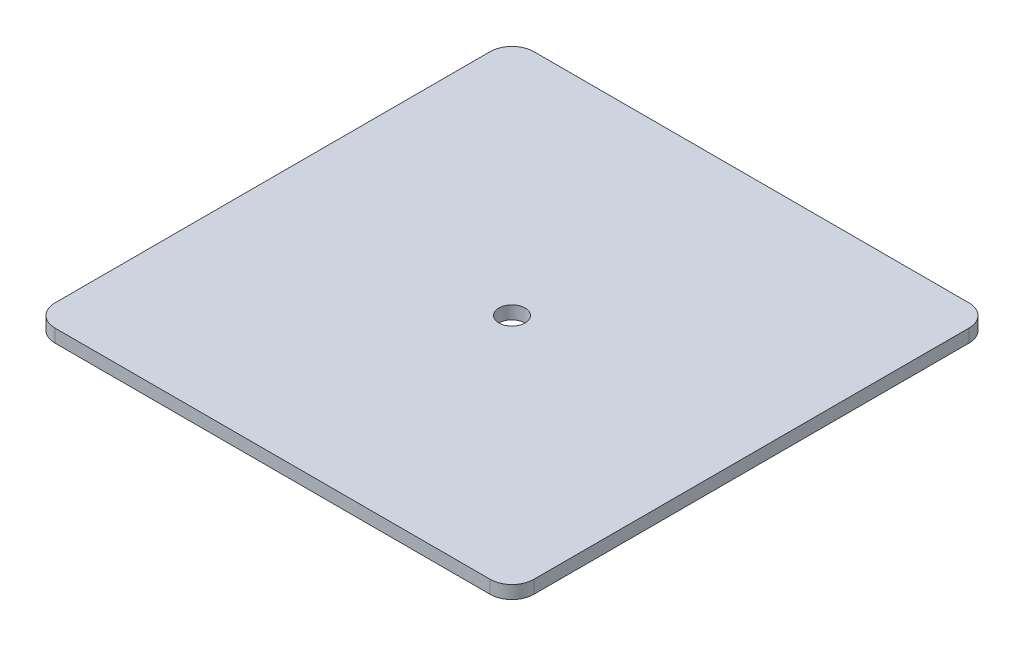
SolidWorks part; units mm, degrees
material "Acrylic (Medium-high impact)"
ref_plane "Front" through (0, 0, 0) normal (0, 0, 1) x (1, 0, 0)
ref_plane "Top" through (0, 0, 0) normal (0, 1, 0) x (1, 0, 0)
ref_plane "Right" through (0, 0, 0) normal (1, 0, 0) x (0, 0, -1)
sketch "Sketch1" plane through (0, 0, 0) normal (0, 1, 0) x (1, 0, 0)
  line L1 (110, -110) -> (-110, -110)
  line L2 (110, -110) -> (110, 110)
  line L3 (110, 110) -> (-110, 110)
  line L4 (-110, -110) -> (-110, 110)
  line L5 (0, 110) -> (0, -110) construction
  line L6 (110, 0) -> (-110, 0) construction
  point P0 (0, 0)
  dimension "D1" = 220
  dimension "D2" = 220
extrude "Boss-Extrude1" add sketch "Sketch1" along normal blind 6
sketch "Sketch2" plane through (0, 6, 0) normal (0, 1, 0) x (1, 0, 0)
  circle A0 centre (0, 0) radius 6
  dimension "D1" = 12
extrude "Cut-Extrude1" cut sketch "Sketch2" against normal blind 51
fillet "Fillet1" radius 10 4 edges at (-110, 3, -110) (-110, 3, 110) (110, 3, -110) (110, 3, 110)
